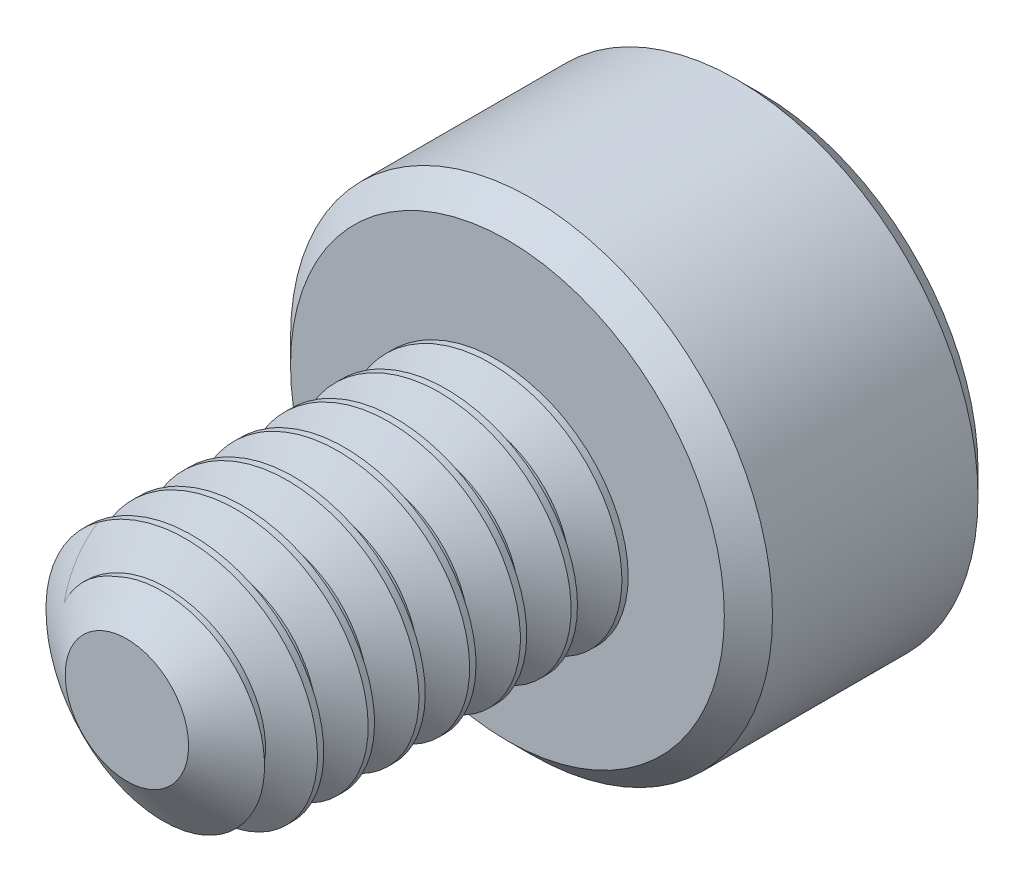
SolidWorks part; units mm, degrees
ref_plane "Front Plane" through (0, 0, 0) normal (0, 0, 1) x (1, 0, 0)
ref_plane "Top Plane" through (0, 0, 0) normal (0, 1, 0) x (1, 0, 0)
ref_plane "Right Plane" through (0, 0, 0) normal (1, 0, 0) x (0, 0, -1)
sketch "Sketch1" plane through (0, 0, 0) normal (0, 0, 1) x (1, 0, 0)
  circle A0 centre (0, 0) radius 1
  dimension "OD" = 2
extrude "Extrude1" add sketch "Sketch1" against normal blind 3
sketch "Sketch2" plane through (0, 0, 0) normal (0, 0, 1) x (1, 0, 0)
  circle A0 centre (0, 0) radius 1 construction
  circle A1 centre (0, 0) radius 1
curve "Helix/Spiral1" pitch 0.4 height 3.4 radius 1 centre (0, 0, 0) axis (0, 0, -1) start towards (0, 1, 0) parameters "pitch"=0.4
sketch "Sketch3" plane through (0, 0, 0) normal (1, 0, 0) x (0, 0, -1)
  line L0 (-0.35, 1) -> (-0.2, 0.7402)
  line L1 (-0.2, 0.7402) -> (-0.15, 0.7402)
  line L2 (-0.15, 0.7402) -> (0, 1)
  line L3 (-0.35, 1) -> (0, 1)
  line L4 (-0.175, 1) -> (-0.175, 0.7402) construction
  line L5 (-0.275, 0.8701) -> (-0.075, 0.8701) construction
  line L6 (0, 1) -> (0, -1) construction
  dimension "D1" = 0.05
  dimension "D2" = 0.2
  dimension "D3" = 60
sweep "Cut-Sweep1" cut profiles "Sketch3" path "Helix/Spiral1"
sketch "Sketch4" plane through (0, 0, 0) normal (1, 0, 0) x (0, 0, -1)
  line L0 (0.3598, 1) -> (0, 0.4862)
  line L1 (0, 0.4862) -> (0, 1)
  line L2 (0.3598, 1) -> (0, 1)
  line L3 (-0.35, 1) -> (0, 1) construction
  line L4 (0, 0) -> (7.0209, 0) construction
  dimension "D1" = 55
  dimension "D2" = 0.254
revolve "Cut-Revolve1" cut sketch "Sketch4" angle 360 about L4
sketch "Sketch6" plane through (0, 0, -3) normal (0, 0, -1) x (-1, 0, 0)
  circle A0 centre (0, 0) radius 1.9
  dimension "head dia" = 3.8
extrude "Extrude2" add sketch "Sketch6" along normal blind 2
sketch "Sketch7" plane through (0, 0, -5) normal (0, 0, -1) x (-1, 0, 0)
  line L1 (0, 0.866) -> (-0.75, 0.433)
  line L2 (-0.75, 0.433) -> (-0.75, -0.433)
  line L3 (-0.75, -0.433) -> (0, -0.866)
  line L4 (0, -0.866) -> (0.75, -0.433)
  line L5 (0.75, -0.433) -> (0.75, 0.433)
  line L6 (0.75, 0.433) -> (0, 0.866)
  circle A0 centre (0, 0) radius 0.75 construction
  dimension "hex dia" = 1.5
extrude "Cut-Extrude1" cut sketch "Sketch7" against normal blind 1.125
sketch "Sketch8" plane through (0, 0, -5) normal (0, 0, -1) x (-1, 0, 0)
  circle A0 centre (0, 0) radius 0.866
extrude "Cut-Extrude2" cut sketch "Sketch8" against normal through all draft 45
chamfer "Chamfer1" distance 0.19 angle 45 2 edges at (-1.9, 0, -5) (-1.9, 0, -3)
sketch "Sketch10" plane through (0, 0, -3) normal (0, 0, 1) x (1, 0, 0)
  circle A1 centre (0, 0) radius 1
  circle A2 centre (0, 0) radius 1
  dimension "D1" = 0
ref_plane "Plane1" through (0, 0, 0) normal (0, 0, 1) x (1, 0, 0)
extrude "partial thread" [suppressed] add sketch "Sketch10" along normal up to surface (2 mm away) separate body up to plane "Plane1"
chamfer "Chamfer2" [suppressed] distance 0.04 angle 45
combine bodies "Combine1" [suppressed] operation type add bodies to combine 107 108
sketch "Sketch9" plane through (0, 0, 0) normal (1, 0, 0) x (0, 0, -1)
  line L0 (0, 1) -> (0, -1) construction
  line L1 (1, 1) -> (1, -1) construction
  dimension "D1" = 1
equation "\"D3@Helix/Spiral1\" = \"screw length@Extrude1\"+\"pitch@Helix/Spiral1\""
equation "\"D1@Sketch3\" = \"pitch@Helix/Spiral1\"*.125"
equation "\"D2@Sketch3\" = \"pitch@Helix/Spiral1\"*.5"
equation "\"D1@Cut-Extrude1\" = \"hex dia@Sketch7\"*.75"
equation "\"D1@Chamfer1\" = \"head dia@Sketch6\"*.05"
equation "\"D1@Sketch9\" = \"pitch@Helix/Spiral1\"*2.5"
equation "\"D1@Chamfer2\"=\"OD@Sketch1\"*.02"
